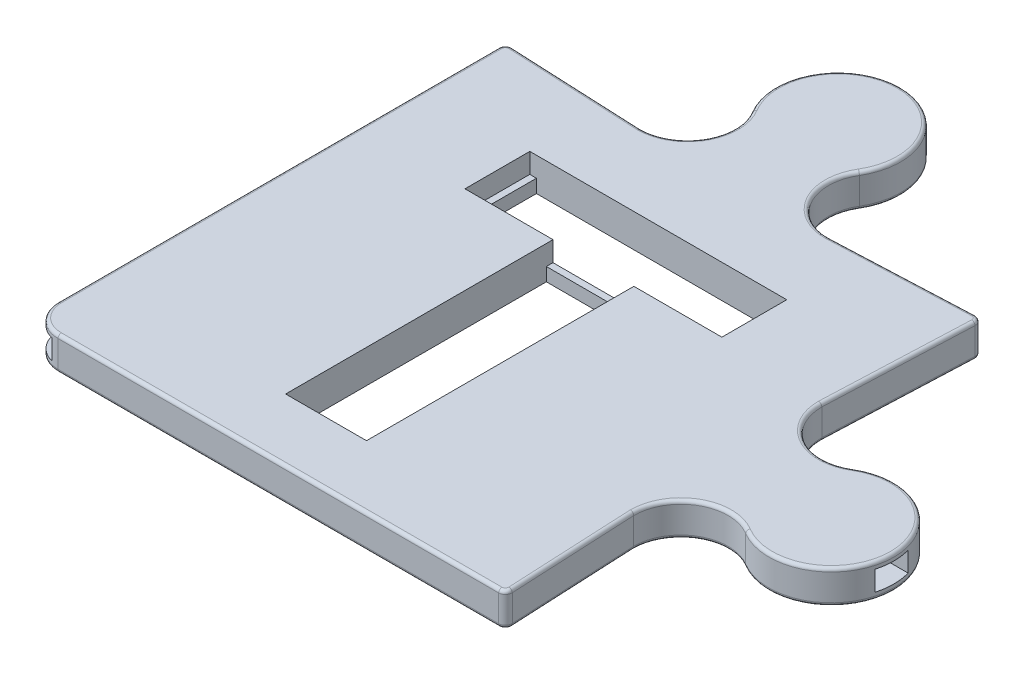
SolidWorks part; units mm, degrees
ref_plane "Front Plane" through (0, 0, 0) normal (0, 0, 1) x (1, 0, 0)
ref_plane "Top Plane" through (0, 0, 0) normal (0, 1, 0) x (1, 0, 0)
ref_plane "Right Plane" through (0, 0, 0) normal (1, 0, 0) x (0, 0, -1)
sketch "Sketch1" plane through (0, 0, 0) normal (0, 1, 0) x (1, 0, 0)
  line L0 (-31, -36) -> (37, -36) construction
  line L1 (-36, 37) -> (-36, -31) construction
  line L2 (-14.1421, 36) -> (-36, 37) construction
  line L3 (37, 37) -> (14.1421, 36) construction
  line L4 (36, 13.1421) -> (37, 37) construction
  line L5 (37, -36) -> (36, -15.1421) construction
  line L6 (-35.4, 36.3719) -> (-35.4, -31)
  line L7 (-36, 36) -> (36, 36) construction
  line L8 (-36, 36) -> (-36, -36) construction
  line L9 (-36, -36) -> (36, -36) construction
  line L10 (36, 36) -> (36, -36) construction
  line L11 (-31, -35.4) -> (36.3705, -35.4)
  line L12 (36.3705, -35.4) -> (35.4, -15.1568)
  line L13 (35.4, 13.155) -> (36.3732, 36.372)
  line L14 (36.3732, 36.372) -> (14.1555, 35.4)
  line L15 (-14.1562, 35.4) -> (-35.4, 36.3719)
  line L16 (-30, -24) -> (30, -24) construction
  line L17 (-30, 29) -> (30, 29) construction
  line L18 (-30, 29) -> (-30, -31) construction
  line L19 (-30, -31) -> (30, -31) construction
  line L20 (30, 29) -> (30, -31) construction
  line L21 (-30, 24) -> (30, 24) construction
  line L22 (-30, 24) -> (-30, -26) construction
  line L23 (-30, -26) -> (30, -26) construction
  line L24 (30, 24) -> (30, -26) construction
  arc A0 (-36, -31) -> (-31, -36) centre (-31, -31) ccw construction
  arc A1 (-14.1421, 36) -> (-8.571, 45.8485) centre (-14.1421, 42.5) ccw construction
  arc A2 (8.571, 45.8485) -> (-8.571, 45.8485) centre (0, 51) ccw construction
  arc A3 (8.571, 45.8485) -> (14.1421, 36) centre (14.1421, 42.5) ccw construction
  arc A4 (36, 13.1421) -> (45.8485, 7.571) centre (42.5, 13.1421) ccw construction
  arc A5 (45.8485, -9.571) -> (45.8485, 7.571) centre (51, -1) ccw construction
  arc A6 (45.8485, -9.571) -> (36, -15.1421) centre (42.5, -15.1421) ccw construction
  arc A7 (-35.4, -31) -> (-31, -35.4) centre (-31, -31) ccw
  arc A8 (46.1576, -9.0567) -> (35.4, -15.1568) centre (42.5, -15.1421) ccw
  arc A9 (46.1576, -9.0567) -> (46.1576, 7.0567) centre (51, -1) ccw
  arc A10 (35.4, 13.155) -> (46.1576, 7.0567) centre (42.5, 13.1421) ccw
  arc A11 (8.0567, 46.1576) -> (14.1555, 35.4) centre (14.1421, 42.5) ccw
  arc A12 (8.0567, 46.1576) -> (-8.0567, 46.1576) centre (0, 51) ccw
  arc A13 (-14.1562, 35.4) -> (-8.0567, 46.1576) centre (-14.1421, 42.5) ccw
  point P32 (36, 0)
  point P34 (0, 36)
  dimension "D5" = 6.5
  dimension "D6" = 10
  dimension "D7" = 6.5
  dimension "D13" = 5
  dimension "D9" = 10
  dimension "D11" = 6.5
  dimension "D12" = 6.5
  dimension "D1" = 72
  dimension "D2" = 1
  dimension "D3" = 1
  dimension "D4" = 15
  dimension "D8" = 1
  dimension "D10" = 35
  dimension "D14" = 15
  dimension "D15" = 36
  dimension "D16" = 1
  dimension "D18" = 60
  dimension "D19" = 60
  dimension "D20" = 5
  dimension "D21" = 6
  dimension "D22" = 5
  dimension "D23" = 50
  dimension "D24" = 2
  dimension "D17" = 0.6
extrude "Boss-Extrude1" add sketch "Sketch1" along normal blind 5
sketch "Sketch6" plane through (0, 0, 0) normal (0, -1, 0) x (1, 0, 0)
  line L0 (-35.4, -36.3719) -> (-35.4, 31) construction
  line L1 (-35.4, 17.9) -> (-27.4, 17.9)
  line L2 (-35.4, 17.9) -> (-35.4, -16.1)
  line L3 (-35.4, -16.1) -> (-27.4, -16.1)
  line L4 (-27.4, 17.9) -> (-27.4, -16.1)
  line L5 (-31, 35.4) -> (36.3705, 35.4) construction
  line L6 (-35.4, 14.65) -> (-30.4, 14.65)
  line L7 (-35.4, 14.65) -> (-35.4, -12.85)
  line L8 (-35.4, -12.85) -> (-30.4, -12.85)
  line L9 (-30.4, 14.65) -> (-30.4, -12.85)
  point P15 (-27.4, 0.9)
  point P16 (-30.4, 0.9)
  line M28 (-35.4, 31) -> (-35.4, -36.3719)
  dimension "D1" = 8
  dimension "D2" = 20.75
  dimension "D3" = 27.5
  dimension "D4" = 5
  dimension "D5" = 34
extrude "Cut-Extrude3" cut sketch "Sketch6" against normal blind 3 from offset 1 contours L6 L9 L8 L3 L4 L1 M28 | L9 L6 L2 L8 region at (-29.8665, 0, 0.9) region at (-32.9, 0, 0.9) offset against normal yes
extrude "Cut-Extrude4" cut sketch "Sketch6<3>" against normal up to next contours L9 L6 L2 L8 region at (-32.9, 0, 0.9)
sketch "Sketch6<3>" plane through (0, 0, 0) normal (0, -1, 0) x (1, 0, 0) same geometry as "Sketch6"
sketch "Sketch8" plane through (0, 0, 0) normal (0, -1, 0) x (1, 0, 0)
  line L1 (-2.5, -51.4) -> (2.5, -51.4)
  line L2 (-2.5, -51.4) -> (-2.5, -60.4)
  line L3 (-2.5, -60.4) -> (2.5, -60.4)
  line L4 (2.5, -51.4) -> (2.5, -60.4)
  line L5 (51.4, 3.5) -> (60.4, 3.5)
  line L6 (51.4, 3.5) -> (51.4, -1.5)
  line L7 (51.4, -1.5) -> (60.4, -1.5)
  line L8 (60.4, 3.5) -> (60.4, -1.5)
  arc A0 (-8.0567, -46.1576) -> (8.0567, -46.1576) centre (0, -51) ccw construction
  arc A1 (46.1576, -7.0567) -> (46.1576, 9.0567) centre (51, 1) ccw construction
  point P4 (0, -60.4)
  point P13 (60.4, 1)
  dimension "D1" = 5
  dimension "D2" = 9
  dimension "D3" = 5
  dimension "D4" = 9
extrude "Cut-Extrude5" cut sketch "Sketch8" against normal blind 3 from offset 1 offset against normal yes
sketch "Sketch9" plane through (0, 0, 0) normal (0, -1, 0) x (1, 0, 0)
  line L0 (-31, 35.4) -> (36.3705, 35.4) construction
  line L1 (-35.4, 14.65) -> (-35.4, 31) construction
  line L2 (-31.7636, 35.3332) -> (-35.4, 31) construction
  line L3 (-33.2571, 29.735) -> (-30.0429, 33.565) construction
  line L4 (-30.0429, 33.565) -> (-33.2571, 29.735) construction
  line L5 (-30.0429, 33.565) -> (-32.7119, 35.8048)
  line L6 (-33.2571, 29.735) -> (-35.926, 31.9747)
  line L7 (-32.7119, 35.8048) -> (-35.926, 31.9747)
  circle A0 centre (-31.65, 31.65) radius 2.5
  arc A1 (-31, 35.4) -> (-35.4, 31) centre (-31, 31) ccw construction
  arc M41 (-31, 35.4) -> (-35.4, 31) centre (-31, 31) ccw
  dimension "D1" = 5
  dimension "D3" = 3.75
  dimension "D4" = 5.6569
  dimension "D2" = 3.75
extrude "Cut-Extrude6" cut sketch "Sketch9" against normal blind 3 from offset 1 contours A0 L5 L6 M41 | A0 L5 region at (-33.6239, 0, 33.3064) region at (-31.65, 0, 31.65) offset against normal yes
sketch "Sketch11" plane through (-35.4, 0, 0) normal (-1, 0, 0) x (0, 0, 1)
  line L0 (-13.155, 0) -> (-36.372, 0) construction
  line L1 (-25.1, 3) -> (-19.1, 3)
  line L2 (-25.1, 3) -> (-25.1, 1.5)
  line L3 (-25.1, 1.5) -> (-19.1, 1.5)
  line L4 (-19.1, 3) -> (-19.1, 1.5)
  line L5 (-16.1, 4) -> (-16.1, 1) construction
  line L6 (35.4, 0) -> (15.1568, 0) construction
  line L7 (20.9, 3) -> (26.9, 3)
  line L8 (20.9, 3) -> (20.9, 1.5)
  line L9 (20.9, 1.5) -> (26.9, 1.5)
  line L10 (26.9, 3) -> (26.9, 1.5)
  line L12 (17.9, 4) -> (17.9, 1) construction
  dimension "D1" = 3
  dimension "D2" = 1.5
  dimension "D3" = 3
  dimension "D4" = 6
  dimension "D5" = 3
  dimension "D6" = 1.5
  dimension "D7" = 6
  dimension "D8" = 3
fillet "Fillet1" radius 0.5 17 edges at (-35.4, 0, 22.825) (-34.1113, 0, 34.1113) (2.6853, 0, 35.4) (35.8853, 0, 25.2784) (38.9978, 0, 8.966) (60.4, 0, 1) (38.9986, 0, -6.9655) (35.8866, 0, -24.7635) (25.2643, 0, -35.886) (7.9657, 0, -38.9984) (0, 0, -60.4) (-7.9658, 0, -38.9981) (-24.7781, 0, -35.886) (-35.4, 0, -24.611) (-32.9, 0, -12.85) (-30.4, 0, 0.9) (-32.9, 0, 14.65)
fillet "Fillet2" radius 0.5 13 edges at (-7.9658, 5, -38.9981) (0, 5, -60.4) (7.9657, 5, -38.9984) (25.2643, 5, -35.886) (35.8866, 5, -24.7635) (38.9986, 5, -6.9655) (60.4, 5, 1) (38.9978, 5, 8.966) (35.8853, 5, 25.2784) (2.6853, 5, 35.4) (-34.1113, 5, 34.1113) (-35.4, 5, -2.686) (-24.7781, 5, -35.886)
fillet "Fillet3" radius 1 9 edges at (36.2202, 0.1464, -36.2187) (36.2202, 4.8536, -36.2187) (36.3732, 2.5, -36.372) (-35.2536, 0.1464, -36.2186) (-35.2536, 4.8536, -36.2186) (36.2169, 0.1464, 35.2536) (36.2169, 4.8536, 35.2536) (36.3705, 2.5, 35.4) (-35.4, 2.5, -36.3719)
extrude "Cut-Extrude9" cut sketch "Sketch11" against normal blind 3
chamfer "Chamfer1" distance 1 angle 50 2 edges at (-35.4, 1.5, 23.9) (-35.4, 1.5, -22.1) first distance on face at (-35.4, 2.25, -22.1)
sketch "Sketch12" plane through (0, 5, 0) normal (0, 1, 0) x (1, 0, 0)
  text T0 "T" font "Poppins" height 50
extrude "Cut-Extrude10" cut sketch "Sketch12" against normal through all
sketch "Sketch13" plane through (0, 0, 0) normal (0, -1, 0) x (1, 0, 0)
  line L0 (6.0284, -14.2411) -> (6.0284, 26) construction
  line L1 (-6.1418, -14.2411) -> (6.0284, -14.2411)
  line L2 (-6.1418, -14.2411) -> (-6.1418, -13.2411)
  line L3 (-6.1418, -13.2411) -> (6.0284, -13.2411)
  line L4 (6.0284, -14.2411) -> (6.0284, -13.2411)
  line L5 (-19.3941, -24) -> (19.2807, -24) construction
  line L6 (-19.3941, -14.2411) -> (-18.3941, -14.2411)
  line L7 (-19.3941, -14.2411) -> (-19.3941, -24)
  line L8 (-19.3941, -24) -> (-18.3941, -24)
  line L9 (-18.3941, -14.2411) -> (-18.3941, -24)
  line L11 (19.2807, -14.2411) -> (18.2807, -14.2411)
  line L12 (19.2807, -14.2411) -> (19.2807, -24)
  line L13 (19.2807, -24) -> (18.2807, -24)
  line L14 (18.2807, -14.2411) -> (18.2807, -24)
  line L15 (-6.1418, 26) -> (6.0284, 26)
  line L16 (-6.1418, 26) -> (-6.1418, 25)
  line L17 (-6.1418, 25) -> (6.0284, 25)
  line L18 (6.0284, 26) -> (6.0284, 25)
  dimension "D1" = 1
  dimension "D2" = 1
  dimension "D3" = 1
  dimension "D4" = 1
extrude "Boss-Extrude2" add sketch "Sketch13" against normal blind 2
